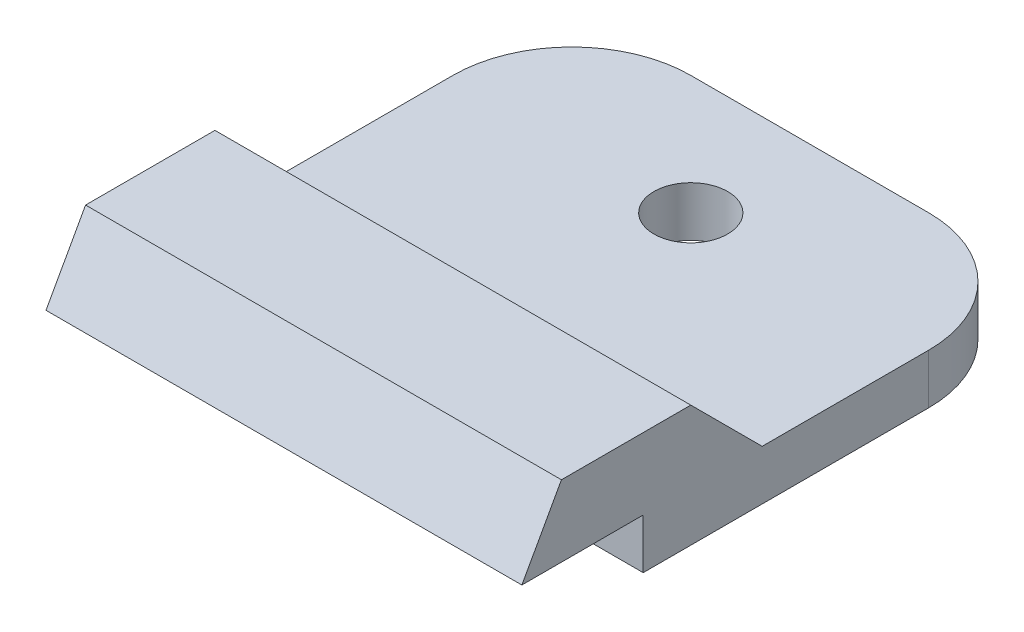
SolidWorks part; units mm, degrees
ref_plane "Front Plane" through (0, 0, 0) normal (0, 0, 1) x (1, 0, 0)
ref_plane "Top Plane" through (0, 0, 0) normal (0, 1, 0) x (1, 0, 0)
ref_plane "Right Plane" through (0, 0, 0) normal (1, 0, 0) x (0, 0, -1)
sketch "Sketch1" plane through (0, 0, 0) normal (1, 0, 0) x (0, 0, -1)
  line L1 (0, 0) -> (7.1, 0)
  line L2 (0, 0) -> (0, -3)
  line L3 (0, -3) -> (7.1, -3)
  line L4 (7.1, 0) -> (7.1, -3)
  line L5 (3.55, -3) -> (3.55, 0) construction
  line L6 (0, -1.5) -> (7.1, -1.5) construction
  line L7 (5.1, -3) -> (22.1, -3)
  line L8 (5.1, -3) -> (5.1, -5.1)
  line L9 (5.1, -5.1) -> (22.1, -5.1)
  line L10 (22.1, -3) -> (22.1, -5.1)
  line L11 (13.6, -5.1) -> (13.6, -3) construction
  line L12 (5.1, -4.05) -> (22.1, -4.05) construction
  point P144 (3.55, -1.5)
  point P350 (13.6, -4.05)
  dimension "D1" = 2.1
  dimension "D2" = 3
  dimension "D3" = 15
  dimension "D4" = 5.1
  dimension "D5" = 2
extrude "Boss-Extrude1" add sketch "Sketch1" along normal blind 20 contours L4 L1 L2 L3 | L10 L7 L3 L8 L9 region at (0, -1.5, -3.55) region at (0, -4.05, -13.6)
sketch "Sketch2" plane through (0, -3, 0) normal (0, 1, 0) x (1, 0, 0)
  line L0 (20, 22.1) -> (0, 22.1) construction
  circle A0 centre (10, 17.1) radius 1.55
  point P4 (10, 22.1)
  dimension "D1" = 3.1
  dimension "D2" = 5
extrude "Cut-Extrude1" cut sketch "Sketch2" against normal blind 20
fillet "Fillet1" radius 5 2 edges at (0, -4.05, -22.1) (20, -4.05, -22.1)
chamfer "Chamfer1" distance 3 angle 45 1 edges at (10, -3, -7.1)
chamfer "Chamfer2" distance 3 angle 29 1 edges at (10, 0, 0) first distance on face at (10, -1.5, 0)
